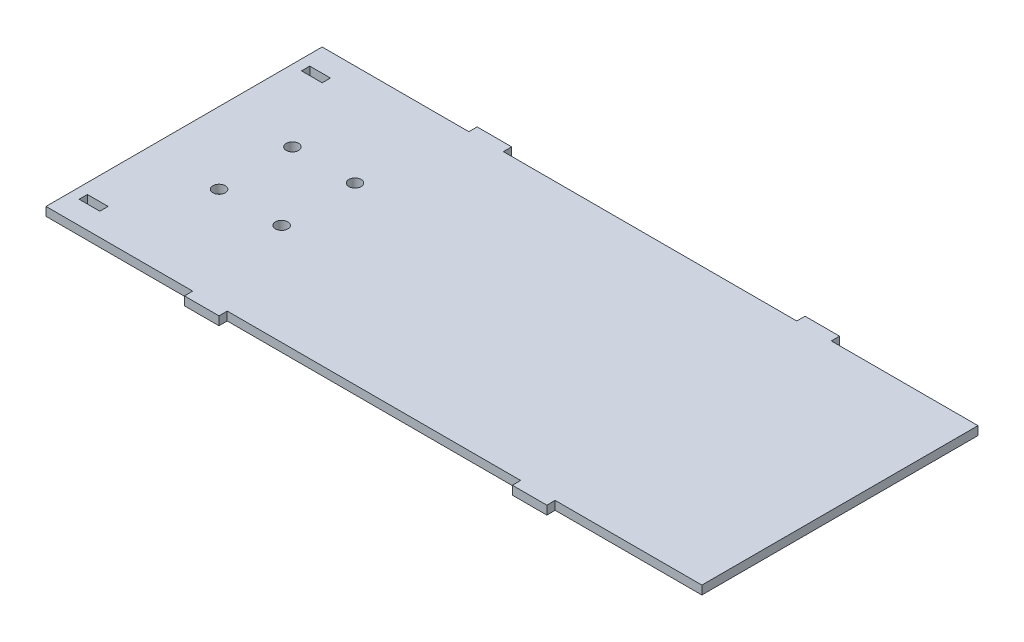
SolidWorks part; units mm, degrees
ref_plane "Front Plane" through (0, 0, 0) normal (0, 0, 1) x (1, 0, 0)
ref_plane "Top Plane" through (0, 0, 0) normal (0, 1, 0) x (1, 0, 0)
ref_plane "Right Plane" through (0, 0, 0) normal (1, 0, 0) x (0, 0, -1)
sketch "Sketch1" plane through (0, 0, 0) normal (0, 1, 0) x (1, 0, 0)
  line L0 (-12.7, 76.2164) -> (228.6, 76.2164) construction
  line L1 (0, 0) -> (41.275, 0)
  line L3 (0, 101.6) -> (41.275, 101.6)
  line L4 (228.6, 0) -> (228.6, 101.6)
  line L9 (0, 0) -> (-12.7, 0)
  line L11 (0, 101.6) -> (-12.7, 101.6)
  line L12 (-12.7, 0) -> (-12.7, 101.6)
  line L13 (107.95, 50.8) -> (228.6, 50.8) construction
  line L14 (174.625, 101.6) -> (228.6, 101.6)
  line L16 (161.925, 101.6) -> (161.925, 104.648)
  line L17 (161.925, 104.648) -> (174.625, 104.648)
  line L18 (174.625, 101.6) -> (174.625, 104.648)
  line L19 (107.95, 76.2164) -> (107.95, 0) construction
  line L20 (174.625, 0) -> (174.625, -3.048)
  line L21 (161.925, 0) -> (161.925, -3.048)
  line L22 (161.925, -3.048) -> (174.625, -3.048)
  line L23 (41.275, 0) -> (41.275, -3.048)
  line L24 (53.975, 0) -> (53.975, -3.048)
  line L25 (53.975, -3.048) -> (41.275, -3.048)
  line L26 (41.275, 101.6) -> (41.275, 104.648)
  line L27 (53.975, 101.6) -> (53.975, 104.648)
  line L28 (53.975, 104.648) -> (41.275, 104.648)
  line L29 (174.625, 0) -> (228.6, 0)
  line L30 (53.975, 101.6) -> (161.925, 101.6)
  line L31 (53.975, 0) -> (161.925, 0)
  point P15 (168.275, 104.648)
  point P16 (168.275, 50.8)
  point P19 (0, 0)
  point P20 (107.95, 50.8)
  dimension "D1" = 228.6
  dimension "D2" = 101.6
  dimension "D3" = 3.048
  dimension "D4" = 12.7
extrude "Main Frame" add sketch "Sketch1" along normal blind 3.175
sketch "Sketch2" plane through (0, 3.175, 0) normal (0, 1, 0) x (1, 0, 0)
  line L0 (0, 50.8) -> (228.6, 50.8) construction
  line L2 (228.6, 0) -> (228.6, 101.6) construction
  line L3 (25.1837, 69.85) -> (25.1837, 31.75) construction
  line L4 (8.6737, 69.85) -> (41.6937, 69.85) construction
  line L5 (8.6737, 69.85) -> (8.6737, 31.75) construction
  line L6 (8.6737, 31.75) -> (41.6937, 31.75) construction
  line L7 (41.6937, 69.85) -> (41.6937, 31.75) construction
  line L8 (0, 101.6) -> (0, 0) construction
  line L9 (41.275, 101.6) -> (-12.7, 101.6) construction
  circle A0 centre (13.6743, 64.2938) radius 2.277
  circle A1 centre (36.6931, 64.2938) radius 2.277
  circle A2 centre (36.6931, 37.3062) radius 2.277
  circle A3 centre (13.6743, 37.3062) radius 2.277
  point P2 (0, 0)
  point P10 (8.6737, 50.8)
  point P26 (0, 0)
  dimension "D1" = 33.02
  dimension "D2" = 38.1
  dimension "D3" = 13.4937
  dimension "D4" = 23.0188
extrude "Front Wheel" cut sketch "Sketch2" against normal through all
sketch "Sketch4" plane through (0, 3.175, 0) normal (0, 1, 0) x (1, 0, 0)
  line L0 (-12.7, 50.8) -> (228.6, 50.8) construction
  line L1 (-8.89, 93.2319) -> (-1.27, 93.2319)
  line L2 (-8.89, 93.2319) -> (-8.89, 90.1839)
  line L3 (-8.89, 90.1839) -> (-1.27, 90.1839)
  line L4 (-1.27, 93.2319) -> (-1.27, 90.1839)
  line L5 (-12.7, 101.6) -> (-12.7, 0) construction
  line L6 (228.6, 0) -> (228.6, 101.6) construction
  line L7 (-8.89, 8.3681) -> (-8.89, 11.4161)
  line L8 (-1.27, 8.3681) -> (-1.27, 11.4161)
  line L9 (-8.89, 11.4161) -> (-1.27, 11.4161)
  line L10 (-8.89, 8.3681) -> (-1.27, 8.3681)
  dimension "D1" = 7.62
  dimension "D2" = 3.048
  dimension "D3" = 3.81
extrude "Sensor Holes" cut sketch "Sketch4" against normal through all
